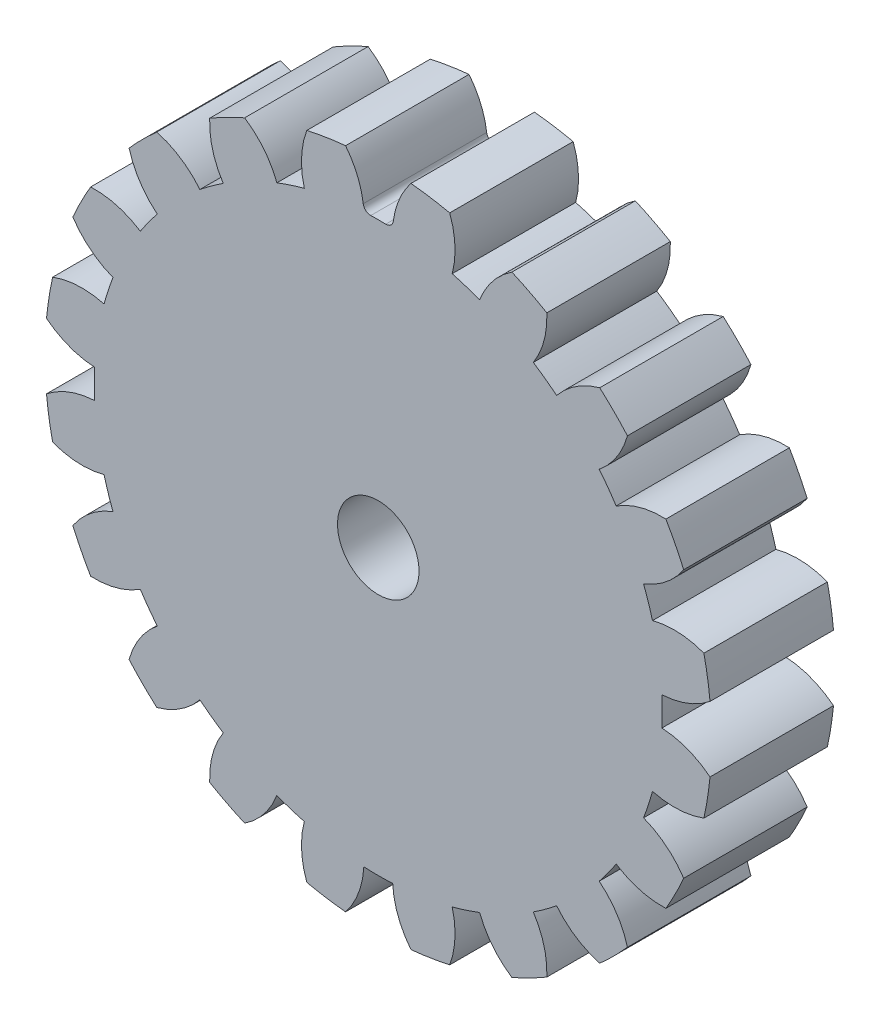
SolidWorks part; units mm, degrees
ref_plane "Front" through (0, 0, 0) normal (0, 0, 1) x (1, 0, 0)
ref_plane "Top" through (0, 0, 0) normal (0, 1, 0) x (1, 0, 0)
ref_plane "Right" through (0, 0, 0) normal (1, 0, 0) x (0, 0, -1)
sketch "Sketch1" plane through (0, 0, 0) normal (0, 0, 1) x (1, 0, 0)
  circle A0 centre (0, 0) radius 11.5
  circle A1 centre (0, 0) radius 13.5
  circle A2 centre (0, 0) radius 12.5
  dimension "D1" = 27
  dimension "D2" = 23
  dimension "D3" = 25
extrude "Boss-Extrude1" add sketch "Sketch1" along normal mid plane 5 contours A1
sketch "Sketch3" plane through (0, 0, 0) normal (0, 0, 1) x (1, 0, 0)
  line L0 (0, 0) -> (0, 13.5) construction
  line L1 (-0.7849, 12.4753) -> (0.7849, 12.4753) construction
  line L2 (-1.4937, 14.4229) -> (0, 10.3189) construction
  line L3 (0, 0) -> (1.692, 13.3935) construction
  line L4 (0.7849, 12.4753) -> (2.3423, 12.2786) construction
  line L5 (0, 0) -> (-0.5842, 11.4852) construction
  circle A0 centre (0, 0) radius 13.5 construction
  arc A1 (-2.3668, 14.3055) -> (-0.5842, 11.4852) centre (-3.98, 11.3124) cw
  arc A2 (2.3668, 14.3055) -> (0.5842, 11.4852) centre (3.98, 11.3124) ccw
  arc A3 (0.5842, 11.4852) -> (-0.5842, 11.4852) centre (0, 0) ccw
  circle A4 centre (0, 0) radius 11.5 construction
  circle A6 centre (0, 0) radius 12.5 construction
  circle A7 centre (0, 0) radius 14.5
  arc A8 (2.3668, 14.3055) -> (-2.3668, 14.3055) centre (0, 0) ccw
  circle A9 centre (0, 0) radius 13.5 construction
  dimension "D3" = 7.2
  dimension "D2" = 20
extrude "Cut-Extrude1" cut sketch "Sketch3" against normal through all both and the other way through all
fillet "Fillet2" radius 0.3 2 edges at (0.5842, 11.4852, 0) (-0.5842, 11.4852, 0)
pattern_circular "CirPattern1" count 20 over 360 about axis through (0, 0, 2.5) along (0, 0, -1) of "Cut-Extrude1"
sketch "Sketch4" plane through (0, 0, 0) normal (0, 0, 1) x (1, 0, 0)
  circle A0 centre (0, 0) radius 1.65
  dimension "D1" = 3.3
extrude "Through_Center_Hole" cut sketch "Sketch4" against normal through all both and the other way through all
equation "\"od\"= 27'outside diameter"
equation "\"n\"= 25'number of teeth"
equation "\"m\"= \"od\" / ( \"n\" + 2 )'module"
equation "\"p\"= \"m\" * pi'pitch"
equation "\"d\"= \"m\" * \"n\"'primitive diameter"
equation "\"da\"= \"d\" + 2 * \"m\"'head diamater"
equation "\"df\"= \"d\" - 2 * \"m\"'foot diameter"
equation "\"D1@Sketch1\"=\"od\""
equation "\"D2@Sketch1\"=\"df\""
equation "\"D3@Sketch1\"=\"d\""
equation "\"D3@Sketch3\"=180/\"n\""
equation "\"D1@Fillet2\"=.3*\"m\""
